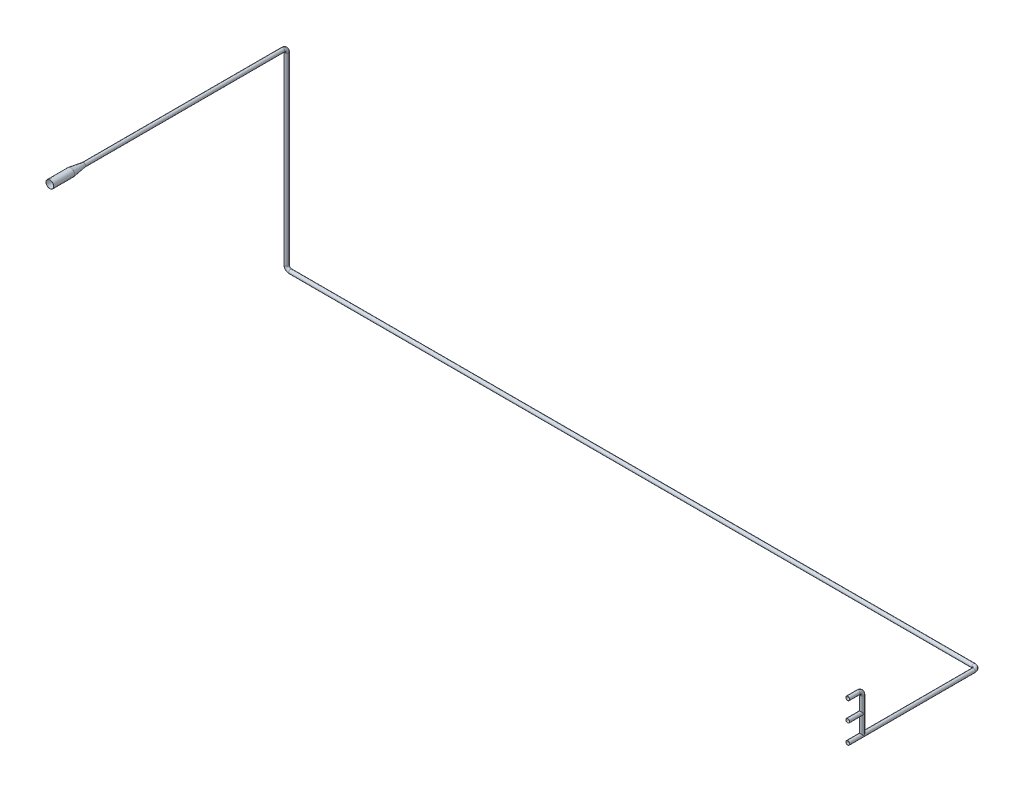
SolidWorks part; units mm, degrees
ref_plane "Plano frontal" through (0, 0, 0) normal (0, 0, 1) x (1, 0, 0)
ref_plane "Plano superior" through (0, 0, 0) normal (0, 1, 0) x (1, 0, 0)
ref_plane "Plano direito" through (0, 0, 0) normal (1, 0, 0) x (0, 0, -1)
sketch3d "3DSketch1"
  line L0 (-34220.2161, -16256.7026, 32891.1068) -> (-34220.2161, -16256.7026, 42891.1068) construction
  line L3 (-34220.2161, -16256.7026, 41048.1482) -> (-34220.2161, -16256.7026, 42561.7037) construction
  line L4 (-34220.2161, -16256.7026, 41048.1482) -> (-34220.2161, -16256.7026, 40885.2507)
  circle A2 centre (-34220.2161, -16256.7026, 41048.1482) radius 30 construction
  point P6 (-34220.2161, -16256.7026, 41018.1482)
  point P7 (-34080.2161, -16256.7026, 41048.1482)
  point P8 (-34080.2161, -16256.7026, 40885.2507)
sweep "Sweep-Thin1" add path "3DSketch1" circular profile diameter 60 parameters "D1"=1, "D3"=60
sketch3d "3DSketch2"
  line L0 (-34220.2161, -16256.7026, 40885.2507) -> (-34220.2161, -16256.7026, 40785.2507) construction
  line L1 (-34220.2161, -16256.7026, 41048.1482) -> (-34220.2161, -16256.7026, 40885.2507) construction
  line L2 (-34220.2161, -16256.7026, 40785.2507) -> (-34220.2161, -16256.7026, 39237.3639)
  line L3 (-34220.2161, -16286.7026, 39207.3639) -> (-34220.2161, -17718.2109, 39207.3639)
  line L4 (-34190.2161, -17748.2109, 39207.3639) -> (-28879.6853, -17748.2109, 39207.3639)
  line L5 (-28849.6853, -17748.2109, 39237.3639) -> (-28849.6853, -17748.2109, 40216.6194)
  arc A0 (-28849.6853, -17748.2109, 39237.3639) -> (-28879.6853, -17748.2109, 39207.3639) centre (-28879.6853, -17748.2109, 39237.3639) ccw
  arc A1 (-34190.2161, -17748.2109, 39207.3639) -> (-34220.2161, -17718.2109, 39207.3639) centre (-34190.2161, -17718.2109, 39207.3639) ccw
  arc A2 (-34220.2161, -16286.7026, 39207.3639) -> (-34220.2161, -16256.7026, 39237.3639) centre (-34220.2161, -16286.7026, 39237.3639) ccw
  point P10 (-28849.6853, -17748.2109, 39207.3639)
  point P11 (-28879.6853, -17718.2109, 39237.3639)
  point P14 (-34220.2161, -17748.2109, 39207.3639)
  point P15 (-34190.2161, -17718.2109, 39177.3639)
  point P18 (-34220.2161, -16256.7026, 39207.3639)
  point P19 (-34190.2161, -16286.7026, 39237.3639)
  dimension "D1" = 30
sweep "Sweep-Thin2" add path "3DSketch2" circular profile diameter 30 parameters "D1"=1, "D3"=30
sketch "Sketch109" plane through (0, 0, 40785.2507) normal (0, 0, 1) x (1, 0, 0)
  circle A0 centre (-34220.2161, -16256.7026) radius 15
  circle A1 centre (-34220.2161, -16256.7026) radius 14
  circle M1 centre (-34220.2161, -16256.7026) radius 14
  circle M2 centre (-34220.2161, -16256.7026) radius 15
  dimension "D1" = 1
  dimension "D2" = 30
extrude "Boss-Extrude2" add sketch "Sketch109" along normal blind 101 draft 8.5 separate body contours M2 M1 | M1 | A1 | A0 region at (-34234.7918, -16256.7026, 40785.2507) region at (-34220.2161, -16256.7026, 40785.2507) draft outward yes
sketch3d "3DSketch4"
  line L0 (-28849.6853, -17748.2109, 40216.6194) -> (-28849.6853, -17748.2109, 39821.6631) construction
  line L1 (-28849.6853, -17748.2109, 39237.3639) -> (-28849.6853, -17748.2109, 40216.6194) construction
  line L2 (-28849.6853, -17748.2109, 40105.2197) -> (-28849.6853, -17598.2109, 40105.2197)
  line L3 (-28849.6853, -17598.2109, 40105.2197) -> (-28849.6853, -17598.2109, 40216.6194)
  line L4 (-28849.6853, -17598.2109, 40105.2197) -> (-28849.6853, -17478.2109, 40105.2197)
  line L5 (-28849.6853, -17448.2109, 40135.2197) -> (-28849.6853, -17448.2109, 40216.6194)
  line L6 (-28849.6853, -17748.2109, 40216.6194) -> (-28849.6853, -17579.9592, 40216.6194) construction
  line L7 (-28849.6853, -17448.2109, 40135.2197) -> (-28849.6853, -17598.2109, 40135.2197) construction
  arc A0 (-28849.6853, -17478.2109, 40105.2197) -> (-28849.6853, -17448.2109, 40135.2197) centre (-28849.6853, -17478.2109, 40135.2197) ccw
  point P11 (-28849.6853, -17448.2109, 40105.2197)
  point P12 (-28819.6853, -17478.2109, 40135.2197)
  dimension "D1" = 30
sweep "Sweep-Thin3" add path "3DSketch4" circular profile diameter 30 parameters "D1"=1, "D3"=30
sweep "Sweep-Thin4" add path "3DSketch4<3>" circular profile diameter 30 parameters "D1"=1, "D3"=30
sketch3d "3DSketch4<3>" same geometry as "3DSketch4"
